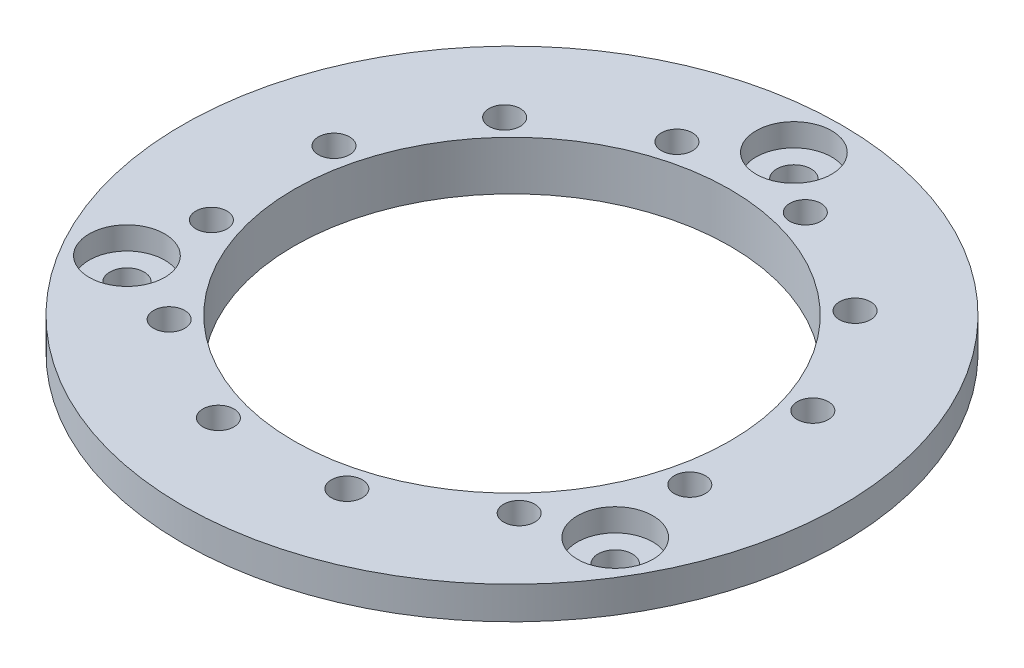
SolidWorks part; units mm, degrees
ref_plane "Front Plane" through (0, 0, 0) normal (0, 0, 1) x (1, 0, 0)
ref_plane "Top Plane" through (0, 0, 0) normal (0, 1, 0) x (1, 0, 0)
ref_plane "Right Plane" through (0, 0, 0) normal (1, 0, 0) x (0, 0, -1)
sketch "Sketch2" plane through (0, 0, 0) normal (0, 1, 0) x (1, 0, 0)
  circle A0 centre (0, 0) radius 63.5
  circle A1 centre (0, 0) radius 42
  dimension "D1" = 127
  dimension "D2" = 84
extrude "Boss-Extrude1" add sketch "Sketch2" along normal blind 9.45
sketch "Sketch15" plane through (0, 9.45, 0) normal (0, 1, 0) x (1, 0, 0)
  line L1 (0, 54.3125) -> (-47.036, -27.1562)
  line L2 (-47.036, -27.1562) -> (47.036, -27.1562)
  line L3 (47.036, -27.1562) -> (0, 54.3125)
  circle A0 centre (0, 0) radius 27.1562 construction
hole_wizard "CBORE for M6 Hex Head Bolt4" positions "3DSketch8" profile "Sketch16" counterbore size "M6" standard "ANSI Metric"
sketch3d "3DSketch8"
  point P0 (0, 9.45, -54.3125)
  point P3 (47.036, 9.45, 27.1562)
  point P6 (-47.036, 9.45, 27.1562)
sketch "Sketch16" plane through (0, 9.45, -54.3125) normal (1, 0, 0) x (0, 0, 1)
  line L0 (0, 0) -> (0, 21.7328)
  line L1 (0, 21.7328) -> (3.3, 19.75)
  line L2 (3.3, 19.75) -> (3.3, 4.38)
  line L3 (3.3, 4.38) -> (7.275, 4.38)
  line L4 (7.275, 4.38) -> (7.275, 0)
  line L5 (7.275, 0) -> (0, 0)
  line L10 (0, 21.7328) -> (-3.3, 19.75) construction
  line L11 (0, -6.35) -> (0, 107.95) construction
  dimension "Hole Dia." = 6.6
  dimension "Hole Depth" = 19.75
  dimension "C'Bore Dia." = 14.55
  dimension "C'Bore Depth" = 4.38
  dimension "Drill Angle" = 118
sketch "Sketch19" plane through (0, 0, 0) normal (0, 1, 0) x (1, 0, 0)
  line L1 (32.2639, 33.6755) -> (11.1036, 45.2958)
  line L2 (11.1036, 45.2958) -> (-13.0318, 44.7791)
  line L3 (-13.0318, 44.7791) -> (-33.6755, 32.2639)
  line L4 (-33.6755, 32.2639) -> (-45.2958, 11.1036)
  line L5 (-45.2958, 11.1036) -> (-44.7791, -13.0318)
  line L6 (-44.7791, -13.0318) -> (-32.2639, -33.6755)
  line L7 (-32.2639, -33.6755) -> (-11.1036, -45.2958)
  line L8 (-11.1036, -45.2958) -> (13.0318, -44.7791)
  line L9 (13.0318, -44.7791) -> (33.6755, -32.2639)
  line L10 (33.6755, -32.2639) -> (45.2958, -11.1036)
  line L11 (45.2958, -11.1036) -> (44.7791, 13.0318)
  line L12 (44.7791, 13.0318) -> (32.2639, 33.6755)
  circle A0 centre (0, 0) radius 45.0478 construction
hole_wizard "M7x1.0 Tapped Hole3" positions "3DSketch15" profile "Sketch22" tap size "M7x1.0" standard "ANSI Metric"
sketch3d "3DSketch15"
  point P0 (-13.0466, 0, -44.8256)
  point P2 (-33.707, 0, -32.286)
  point P4 (-45.4166, 0, -11.1126)
  point P6 (-44.8524, 0, 13.0666)
  point P8 (-32.3315, 0, 33.7328)
  point P10 (-11.1451, 0, 45.4243)
  point P12 (13.0498, 0, 44.8727)
  point P14 (33.7252, 0, 32.3416)
  point P16 (45.4008, 0, 11.1437)
  point P18 (44.9043, 0, -13.0596)
  point P20 (32.303, 0, -33.7941)
  point P22 (11.0897, 0, -45.4287)
sketch "Sketch22" plane through (-13.0466, 0, -44.8256) normal (1, 0, 0) x (0, 0, -1)
  line L0 (0, 0) -> (0, 18.8026)
  line L1 (0, 18.8026) -> (3, 17)
  line L2 (3, 17) -> (3, 0)
  line L5 (3, 0) -> (0, 0)
  line L10 (0, 18.8026) -> (-3, 17) construction
  line L11 (0, -6.35) -> (0, 107.95) construction
  dimension "Tap Drill Dia." = 6
  dimension "Tap Drill Depth" = 17
  dimension "Drill Angle" = 118
cosmetic thread "Hole Thread4" parameters "D1"=14, "D2"=7
cosmetic thread "Hole Thread5" parameters "D1"=14, "D2"=7
cosmetic thread "Hole Thread6" parameters "D1"=14, "D2"=7
cosmetic thread "Hole Thread7" parameters "D1"=14, "D2"=7
cosmetic thread "Hole Thread8" parameters "D1"=14, "D2"=7
cosmetic thread "Hole Thread9" parameters "D1"=14, "D2"=7
cosmetic thread "Hole Thread10" parameters "D1"=14, "D2"=7
cosmetic thread "Hole Thread11" parameters "D1"=14, "D2"=7
cosmetic thread "Hole Thread12" parameters "D1"=14, "D2"=7
cosmetic thread "Hole Thread13" parameters "D1"=14, "D2"=7
cosmetic thread "Hole Thread14" parameters "D1"=14, "D2"=7
cosmetic thread "Hole Thread15" parameters "D1"=14, "D2"=7
sketch "Sketch26" plane through (0, 0, 0) normal (0, 1, 0) x (1, 0, 0)
  circle A0 centre (0, 0) radius 63.5
  dimension "D1" = 127
ref_axis "Axis1" through (0, 9.45, 0) along (0, -1, 0)
sketch "Sketch27" plane through (0, 0, 0) normal (0, 0, 1) x (1, 0, 0)
  line L0 (63.5, 0) -> (-63.5, 0) construction
  line L1 (63.5, 0) -> (58.5912, 0)
  line L2 (63.5, 0) -> (63.5, 3.175)
  line L3 (63.5, 3.175) -> (58.5912, 3.175)
  line L4 (58.5912, 0) -> (58.5912, 3.175)
  line L5 (69.85, 0) -> (-69.85, 0) construction
  line L6 (63.5, 0) -> (63.5, 9.45) construction
  line L7 (63.5, 0) -> (63.5, 9.45)
  line L8 (0, 9.45) -> (0, 0) construction
  line L9 (0, 0) -> (0, 15.4643) construction
  dimension "D1" = 117.1823
  dimension "D2" = 3.175
revolve "Cut-Revolve1" cut sketch "Sketch27" angle 360 about L9 region at (61.0456, 1.5875, 0)
equation "\"ODia\" = 5in"
equation "\"IDiam\"= 84mm"
equation "\"Thick\"= 9.45mm"
equation "\"Lip\"= 3.29mm"
equation "\"D1@Boss-Extrude1\"=\"Thick\""
